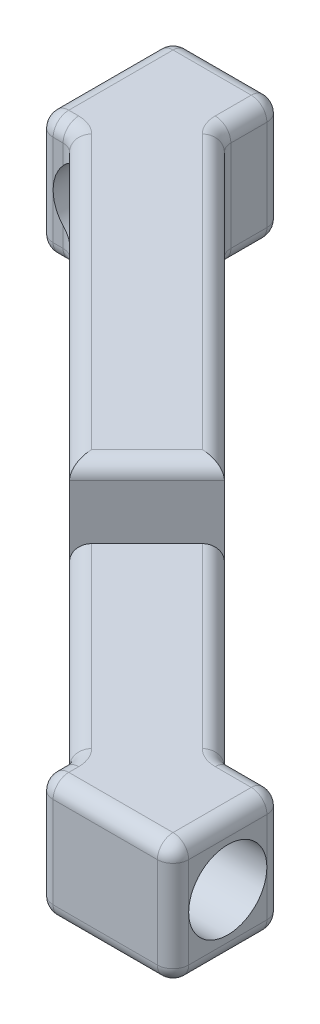
SolidWorks part; units mm, degrees
ref_plane "Front Plane" through (0, 0, 0) normal (0, 0, 1) x (1, 0, 0)
ref_plane "Top Plane" through (0, 0, 0) normal (0, 1, 0) x (1, 0, 0)
ref_plane "Right Plane" through (0, 0, 0) normal (1, 0, 0) x (0, 0, -1)
sketch "Sketch3" plane through (0, 0, 0) normal (0, 1, 0) x (1, 0, 0)
  line L1 (-59.9975, 62.4975) -> (-38.9975, 62.4975)
  line L2 (-59.9975, 62.4975) -> (-59.9975, 36.4975)
  line L3 (-59.9975, 36.4975) -> (-53.8467, 36.4975)
  line L4 (-38.9975, 62.4975) -> (-38.9975, 51.3467)
  line L5 (-59.9975, 62.4975) -> (-38.9975, 36.4975) construction
  line L6 (-59.9975, 36.4975) -> (-38.9975, 62.4975) construction
  line L8 (36.4975, -59.9975) -> (62.4975, -59.9975)
  line L9 (36.4975, -59.9975) -> (36.4975, -53.8467)
  line L10 (51.3467, -38.9975) -> (62.4975, -38.9975)
  line L11 (62.4975, -59.9975) -> (62.4975, -38.9975)
  line L12 (36.4975, -59.9975) -> (62.4975, -38.9975) construction
  line L13 (36.4975, -38.9975) -> (62.4975, -59.9975) construction
  line L14 (-49.4975, 49.4975) -> (49.4975, -49.4975) construction
  line L15 (-98.384, 0) -> (127.6464, 0) construction
  line L16 (-38.9975, 51.3467) -> (51.3467, -38.9975)
  line L18 (36.4975, -53.8467) -> (-53.8467, 36.4975)
  line L19 (36.4975, -38.9975) -> (62.4975, -38.9975) construction
  point P0 (-49.4975, 49.4975)
  point P5 (49.4975, -49.4975)
  point P12 (0, 0)
  dimension "D1" = 140
  dimension "D2" = 26
  dimension "D3" = 26
  dimension "D4" = 21
  dimension "D5" = 21
  dimension "D6" = 45
  dimension "D7" = 21
extrude "Boss-Extrude1" add sketch "Sketch3" along normal blind 37
sketch "Sketch5" plane through (7.8063, 0, -4.5429) normal (-0.7071, 0, 0.7071) x (0.7071, 0, 0.7071)
  line L4 (61.5754, 18.5) -> (-66.1906, 18.5) construction
  line L5 (61.5754, 37) -> (61.5754, 0) construction
  line L6 (61.5754, 37) -> (-66.1906, 37) construction
  line L7 (61.5754, 0) -> (-66.1906, 0) construction
  line L12 (-66.1906, 0) -> (-74.0754, 0) construction
  line L13 (-74.0754, 0) -> (-88.9246, 0) construction
  line L14 (-88.9246, 37) -> (-88.9246, 0) construction
  line L15 (-66.1906, 37) -> (-66.1906, 0) construction
  line L17 (69.4602, 37) -> (61.5754, 37) construction
  line L18 (84.3094, 37) -> (69.4602, 37) construction
  line L19 (84.3094, 37) -> (84.3094, 0) construction
  line L22 (61.5754, 37) -> (12.1924, 37)
  line L23 (-9.8076, 0) -> (-66.1906, 0)
  line L24 (-66.1906, 0) -> (-74.0754, 0)
  line L25 (-74.0754, 0) -> (-88.9246, 0)
  line L26 (-88.9246, 13.5) -> (-88.9246, 0)
  line L29 (69.4602, 37) -> (61.5754, 37)
  line L30 (84.3094, 37) -> (69.4602, 37)
  line L31 (84.3094, 37) -> (84.3094, 23.5)
  line L32 (84.3094, 23.5) -> (12.1924, 23.5)
  line L33 (12.1924, 23.5) -> (12.1924, 37)
  line L34 (-88.9246, 13.5) -> (-9.8076, 13.5)
  line L35 (-9.8076, 13.5) -> (-9.8076, 0)
  line L36 (1.1924, 0) -> (1.1924, 71.3842) construction
  dimension "D1" = 11
  dimension "D2" = 11
  dimension "D3" = 10
  dimension "D4" = 5
extrude "Cut-Extrude1" cut sketch "Sketch5" against normal through all both and the other way through all
sketch "Sketch6" plane through (62.4975, 0, 0) normal (1, 0, 0) x (0, 0, -1)
  line L0 (-49.4975, 11.75) -> (-49.4975, 0) construction
  line L1 (-59.9975, 0) -> (-38.9975, 0) construction
  line L2 (-49.4975, 11.75) -> (-59.9975, 11.75) construction
  line L3 (-59.9975, 23.5) -> (-59.9975, 0) construction
  circle A0 centre (-49.4975, 11.75) radius 7.5
  dimension "D1" = 15
extrude "Cut-Extrude2" cut sketch "Sketch6" against normal through all
sketch "Sketch7" plane through (0, 0, -62.4975) normal (0, 0, -1) x (-1, 0, 0)
  line L0 (49.4975, 25.25) -> (49.4975, 13.5) construction
  line L1 (38.9975, 13.5) -> (59.9975, 13.5) construction
  line L2 (49.4975, 25.25) -> (59.9975, 25.25) construction
  line L3 (59.9975, 37) -> (59.9975, 13.5) construction
  circle A0 centre (49.4975, 25.25) radius 7.5
  dimension "D1" = 15
extrude "Cut-Extrude3" cut sketch "Sketch7" against normal through all
fillet "Fillet1" radius 3 38 edges at (56.9221, 0, 38.9975) (56.9221, 23.5, 38.9975) (-38.9975, 25.25, -51.3467) (26.109, 0, 13.7598) (51.3467, 11.75, 38.9975) (33.8872, 23.5, 21.538) (62.4975, 0, 49.4975) (62.4975, 11.75, 59.9975) (62.4975, 23.5, 49.4975) (62.4975, 11.75, 38.9975) (-6.5533, 0, -4.0533) (-33.9123, 13.5, -16.5631) (-19.0631, 13.5, -31.4123) (-38.9975, 13.5, -56.9221) (-56.9221, 13.5, -36.4975) (-59.9975, 25.25, -36.4975) (-59.9975, 13.5, -49.4975) (-59.9975, 25.25, -62.4975) (-49.4975, 13.5, -62.4975) (-38.9975, 25.25, -62.4975) (-26.1341, 37, -8.7849) (-56.9221, 37, -36.4975) (-59.9975, 37, -49.4975) (-49.4975, 37, -62.4975) (-38.9975, 37, -56.9221) (-11.2849, 37, -23.6341) (9.003, 37, 11.503) (19.038, 23.5, 36.3872) (11.2598, 0, 28.609) (49.4975, 0, 59.9975) (49.4975, 23.5, 59.9975) (36.4975, 11.75, 59.9975) (36.4975, 0, 56.9221) (-53.8467, 16.3199, -36.4975) (-53.8467, 34.1801, -36.4975) (36.4975, 20.6801, 53.8467) (36.4975, 2.8199, 53.8467) (36.4975, 23.5, 56.9221)
equation "\"D2@Sketch3\"=\"D3@Sketch3\""
equation "\"D5@Sketch3\"=\"D4@Sketch3\""
equation "\"D1@Sketch5\"=\"D2@Sketch5\""
equation "\"D4@Sketch5\"=\"D3@Sketch5\"/2"
